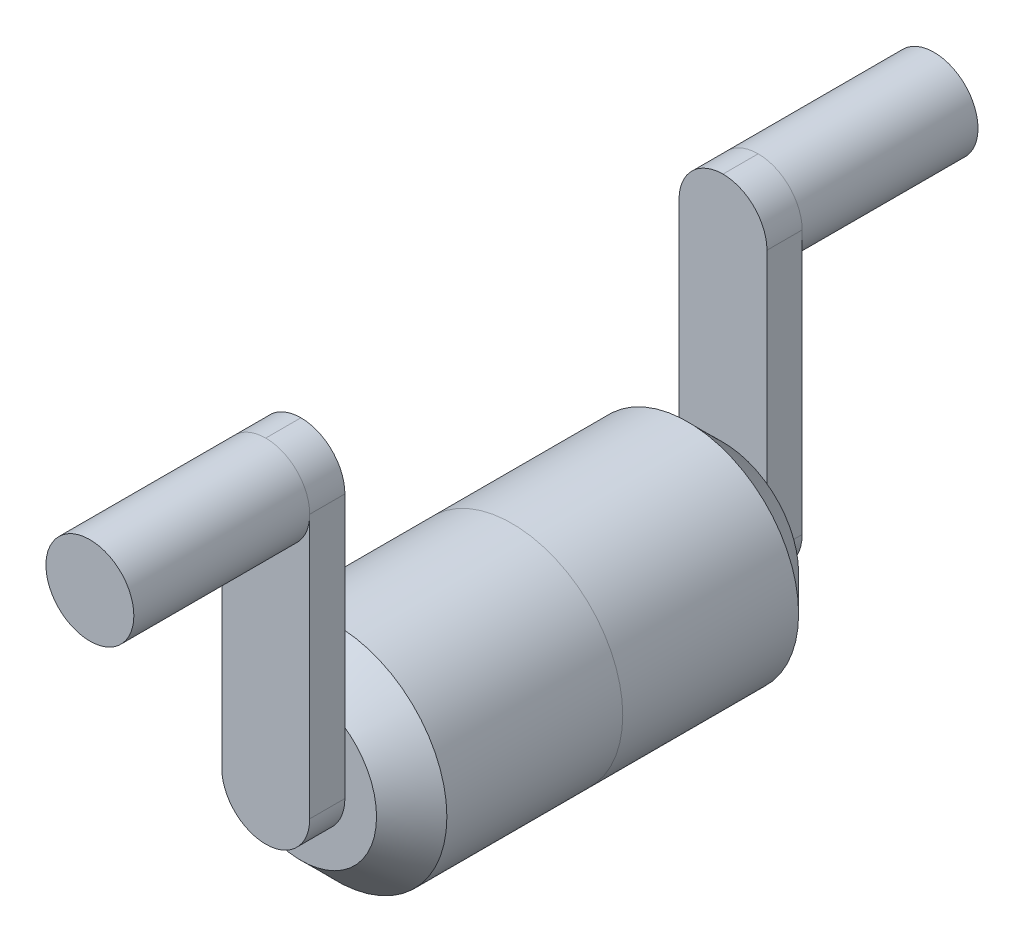
SolidWorks part; units mm, degrees
ref_plane "Front Plane" through (0, 0, 0) normal (0, 0, 1) x (1, 0, 0)
ref_plane "Top Plane" through (0, 0, 0) normal (0, 1, 0) x (1, 0, 0)
ref_plane "Right Plane" through (0, 0, 0) normal (1, 0, 0) x (0, 0, -1)
sketch "Sketch1" plane through (0, 0, 0) normal (0, 0, 1) x (1, 0, 0)
  line L0 (0, 0) -> (0, 6.25) construction
  line L1 (-6.25, 6.25) -> (6.25, 6.25)
  line L2 (-6.25, 6.25) -> (-6.25, -43.75)
  line L3 (-6.25, -43.75) -> (6.25, -43.75)
  line L4 (6.25, 6.25) -> (6.25, -43.75)
  line L5 (0, -37.5) -> (0, -43.75) construction
  circle A0 centre (0, -37.5) radius 15.75
  circle A1 centre (0, 0) radius 6.25
  point P9 (0, 0)
  point P12 (0, 0)
  dimension "D3" = 31.5
  dimension "D1" = 12.5
  dimension "D2" = 50
extrude "Boss-Extrude1" add sketch "Sketch1" along normal blind 30 contours A1 region at (0, 0, 0)
extrude "Boss-Extrude2" add sketch "Sketch1<3>" along normal blind 5 contours A1 L2 A0 L4 | A1 L4 L1 | A1 L1 L2 | A1 | L2 L1 L4 L3 region at (-4.854, 4.854, 0) region at (4.854, 4.854, 0) region at (0, 0, 0) region at (0, -13.4891, 0)
sketch "Sketch1<3>" plane through (0, 0, 0) normal (0, 0, 1) x (1, 0, 0) same geometry as "Sketch1"
extrude "Boss-Extrude3" add sketch "Sketch1<4>" against normal blind 30 separate body contours L2 A0 L4 L3 | L4 A0 L2 L3 | A0 region at (0, -32.9585, 0) region at (-6.6864, -33.3966, 0)
sketch "Sketch1<4>" plane through (0, 0, 0) normal (0, 0, 1) x (1, 0, 0) same geometry as "Sketch1"
ref_plane "Plane1" through (0, 0, -30) normal (0, 0, -1) x (-1, 0, 0)
chamfer "Chamfer1" distance 5 angle 45 1 edges at (15.75, -37.5, 0)
fillet "Fillet1" radius 6.25 4 edges at (-6.25, -43.75, 2.5) (-6.25, 6.25, 2.5) (6.25, -43.75, 2.5) (6.25, 6.25, 2.5)
mirror "Mirror1" about plane through (0, 0, -30) normal (0, 0, -1) of bodies 103 102
